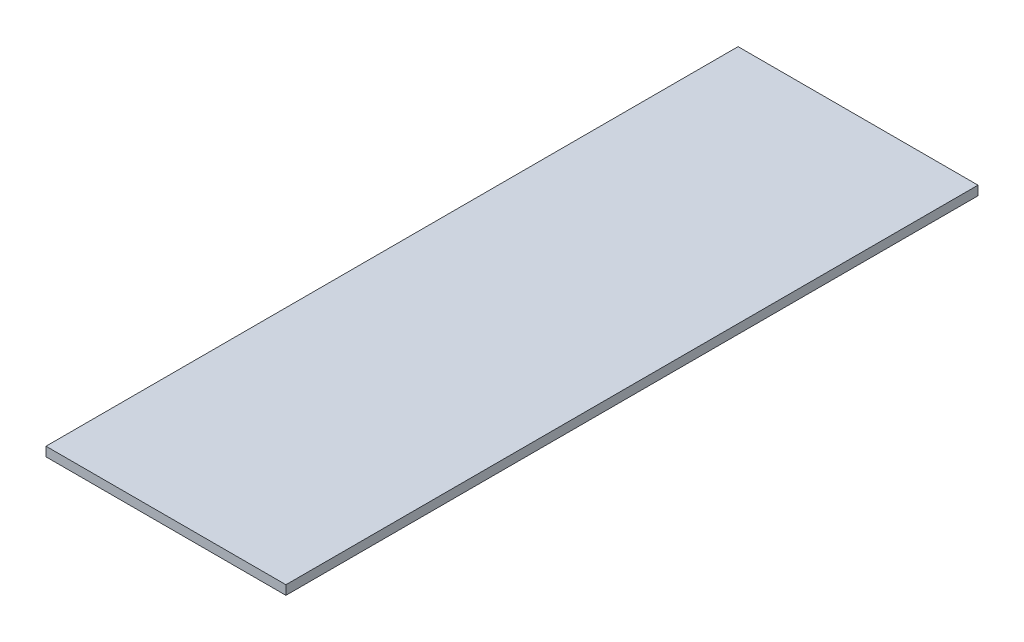
SolidWorks part; units mm, degrees
ref_plane "Front Plane" through (0, 0, 0) normal (0, 0, 1) x (1, 0, 0)
ref_plane "Top Plane" through (0, 0, 0) normal (0, 1, 0) x (1, 0, 0)
ref_plane "Right Plane" through (0, 0, 0) normal (1, 0, 0) x (0, 0, -1)
sketch "Sketch1" plane through (0, 25.5, 0) normal (0, 1, 0) x (1, 0, 0)
  line L0 (0, 30) -> (0, 30.25)
  line L1 (-13, 30) -> (13, 30)
  line L2 (-13, 30) -> (-13, -45)
  line L3 (-13, -45) -> (13, -45)
  line L4 (13, 30) -> (13, -45)
  line L5 (13.25, 30.25) -> (-13.25, 30.25) construction
  point P8 (0, 0)
  dimension "D1" = 75
  dimension "D2" = 26
  dimension "D3" = 0.25
extrude "Boss-Extrude1" add sketch "Sketch1" along normal blind 1 contours L1 L4 L3 L2
